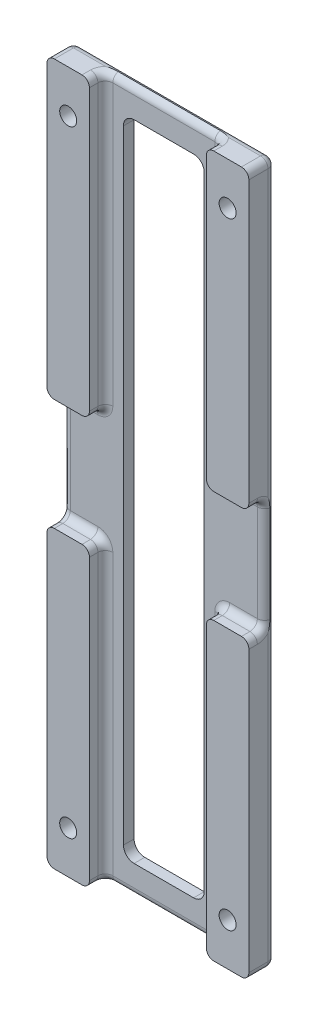
SolidWorks part; units mm, degrees
note: The reader was unsure of these and kept them because the rebuilt part matched: shared geometry of "Sketch1<3>".
ref_plane "Front Plane" through (0, 0, 0) normal (1, 0, 0) x (0, 1, 0)
ref_plane "Top Plane" through (0, 0, 0) normal (0, 0, 1) x (0, 1, 0)
ref_plane "Right Plane" through (0, 0, 0) normal (0, 1, 0) x (-1, 0, 0)
sketch "Sketch1" plane through (0, 0, 0) normal (0, 0, 1) x (0, 1, 0)
  line L0 (0, 19) -> (124, 19) construction
  line L1 (8, 34) -> (124, 34) construction
  line L2 (8, 34) -> (8, 4) construction
  line L3 (8, 4) -> (124, 4) construction
  line L4 (124, 34) -> (124, 4) construction
  line L5 (0, 38) -> (132, 38)
  line L6 (0, 38) -> (0, 0)
  line L7 (0, 0) -> (132, 0)
  line L8 (132, 38) -> (132, 0)
  line L13 (0, 8) -> (55.5, 8)
  line L14 (0, 8) -> (0, 0)
  line L15 (0, 0) -> (55.5, 0)
  line L16 (55.5, 8) -> (55.5, 0)
  line L21 (76.5, 8) -> (132, 8)
  line L22 (76.5, 8) -> (76.5, 0)
  line L23 (76.5, 0) -> (132, 0)
  line L24 (132, 8) -> (132, 0)
  line L25 (76.5, 8) -> (132, 8)
  line L26 (76.5, 0) -> (132, 0)
  line L27 (0, 8) -> (55.5, 8)
  line L28 (0, 0) -> (55.5, 0)
  line L30 (0, 0) -> (132, 0)
  line L31 (0, 8) -> (55.5, 8)
  line L32 (0, 0) -> (55.5, 0)
  line L33 (76.5, 8) -> (132, 8)
  line L34 (76.5, 0) -> (132, 0)
  line L35 (76.5, 8) -> (132, 8)
  line L36 (76.5, 0) -> (132, 0)
  line L37 (0, 8) -> (55.5, 8)
  line L38 (0, 0) -> (55.5, 0)
  line L41 (0, 38) -> (55.5, 38)
  line L42 (0, 30) -> (55.5, 30)
  line L43 (76.5, 38) -> (132, 38)
  line L44 (76.5, 30) -> (132, 30)
  line L45 (76.5, 38) -> (132, 38)
  line L46 (76.5, 30) -> (132, 30)
  line L47 (0, 38) -> (55.5, 38)
  line L48 (0, 30) -> (55.5, 30)
  line L49 (0, 38) -> (132, 38)
  line L50 (0, 38) -> (55.5, 38)
  line L51 (0, 30) -> (55.5, 30)
  line L52 (76.5, 38) -> (132, 38)
  line L53 (76.5, 30) -> (132, 30)
  line L54 (132, 30) -> (132, 38)
  line L55 (76.5, 38) -> (132, 38)
  line L56 (76.5, 30) -> (76.5, 38)
  line L57 (76.5, 30) -> (132, 30)
  line L58 (55.5, 30) -> (55.5, 38)
  line L59 (0, 38) -> (55.5, 38)
  line L60 (0, 30) -> (0, 38)
  line L61 (0, 30) -> (55.5, 30)
  circle A0 centre (8, 34) radius 1.6
  circle A1 centre (8, 4) radius 1.6
  circle A2 centre (124, 34) radius 1.6
  circle A3 centre (124, 4) radius 1.6
  point P12 (0, 0)
  point P15 (132, 54.2745)
  point P20 (0, 0)
  dimension "D3" = 3.2
  dimension "D1" = 116
  dimension "D2" = 30
  dimension "D4" = 8
  dimension "D5" = 8
  dimension "D6" = 8
  dimension "D7" = 21
extrude "Boss-Extrude1" add sketch "Sketch1" along normal blind 2 contours L58 L42 L6 L13 L16 L7 L22 L21 L8 L44 L56 L5 | L42 L58 L5 L6 A0 | L56 L44 L8 L5 A2 | L21 L22 L7 L8 A3 | L16 L13 L6 L7 A1
extrude "Boss-Extrude2" add sketch "Sketch1<3>" along normal blind 3 from surface at 2 contours L42 L58 L5 L6 A0 | L56 L44 L8 L5 A2 | L21 L22 L7 L8 A3 | L16 L13 L6 L7 A1 starting at face at (-19, 66, 2)
sketch "Sketch1<3>" plane through (0, 0, 0) normal (0, 0, 1) x (0, 1, 0) same geometry as "Sketch1"
fillet "Fillet1" radius 1.4 32 edges at (-30, 0, 3.5) (-8, 0, 3.5) (-38, 55.5, 3.5) (-38, 76.5, 3.5) (-30, 132, 3.5) (-8, 132, 3.5) (0, 76.5, 3.5) (0, 55.5, 3.5) (-19, 0, 0) (0, 66, 0) (-19, 132, 0) (-38, 66, 0) (-19, 0, 2) (-30, 27.75, 2) (-34, 55.5, 2) (-38, 66, 2) (-34, 76.5, 2) (-30, 104.25, 2) (-19, 132, 2) (-8, 104.25, 2) (-4, 76.5, 2) (0, 66, 2) (-4, 55.5, 2) (-8, 27.75, 2) (-8, 55.5, 3.5) (-8, 76.5, 3.5) (-30, 76.5, 3.5) (-30, 55.5, 3.5) (0, 0, 2.5) (-38, 0, 2.5) (0, 132, 2.5) (-38, 132, 2.5)
sketch "Sketch2" plane through (0, 0, 2) normal (0, 0, 1) x (1, 0, 0)
  line L0 (-36.6, 66) -> (-1.4, 66) construction
  line L1 (-24.6, 126.6) -> (-13.4, 126.6)
  line L2 (-26.6, 124.6) -> (-26.6, 7.4)
  line L3 (-24.6, 5.4) -> (-13.4, 5.4)
  line L4 (-11.4, 124.6) -> (-11.4, 7.4)
  line L5 (-36.6, 75.1) -> (-36.6, 56.9) construction
  line L6 (-1.4, 56.9) -> (-1.4, 75.1) construction
  line L7 (-9.4, 130.6) -> (-28.6, 130.6) construction
  line L8 (-28.6, 130.6) -> (-28.6, 77.9) construction
  line L9 (-9.4, 77.9) -> (-9.4, 130.6) construction
  arc A0 (-26.6, 7.4) -> (-24.6, 5.4) centre (-24.6, 7.4) ccw
  arc A1 (-13.4, 5.4) -> (-11.4, 7.4) centre (-13.4, 7.4) ccw
  arc A2 (-13.4, 126.6) -> (-11.4, 124.6) centre (-13.4, 124.6) cw
  arc A3 (-24.6, 126.6) -> (-26.6, 124.6) centre (-24.6, 124.6) ccw
  dimension "D4" = 2
  dimension "D1" = 4
  dimension "D2" = 2
  dimension "D3" = 2
extrude "Cut-Extrude1" cut sketch "Sketch2" against normal through all
